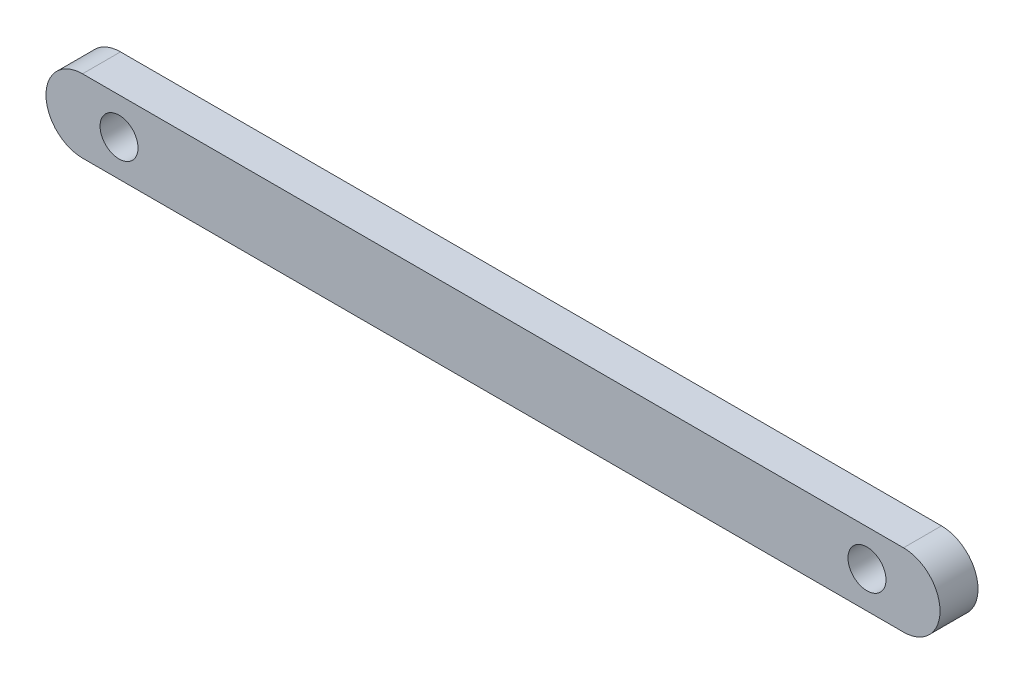
SolidWorks part; units mm, degrees
material "1060 Alloy"
ref_plane "Front Plane" through (0, 0, 0) normal (0, 0, 1) x (1, 0, 0)
ref_plane "Top Plane" through (0, 0, 0) normal (0, 1, 0) x (1, 0, 0)
ref_plane "Right Plane" through (0, 0, 0) normal (1, 0, 0) x (0, 0, -1)
ref_axis "X-axis" through (-88.99, 0, 0) along (1, 0, 0)
ref_axis "Y-axis" through (0, 55, 0) along (0, -1, 0)
ref_axis "Z-axis" through (0, 0, -88.99) along (0, 0, 1)
sketch "Sketch1" plane through (0, 0, 0) normal (0, 0, 1) x (1, 0, 0)
  line L0 (35.687, 0) -> (-35.687, 0) construction
  line L1 (35.687, -3.175) -> (-35.687, -3.175)
  line L2 (35.687, 3.175) -> (-35.687, 3.175)
  arc A0 (35.687, -3.175) -> (35.687, 3.175) centre (35.687, 0) ccw
  arc A1 (-35.687, 3.175) -> (-35.687, -3.175) centre (-35.687, 0) ccw
  point P2 (0, 0)
  point P8 (38.862, 0)
  point P9 (-38.862, 0)
  dimension "D1" = 6.35
  dimension "D2" = 77.724
extrude "Boss-Extrude1" add sketch "Sketch1" against normal blind 3.302
hole_wizard "1/4 (0.13) Diameter Hole1" positions "Sketch2" profile "Sketch3" hole size "1/4" standard "ANSI Inch" end condition through all
sketch "Sketch2" plane through (0, 0, 0) normal (0, 0, 1) x (1, 0, 0)
  line L0 (-32.512, 0) -> (32.512, 0) construction
  arc A0 (-35.687, 3.175) -> (-35.687, -3.175) centre (-35.687, 0) ccw construction
  point P0 (-32.512, 0)
  point P2 (32.512, 0)
  point P12 (-38.862, 0)
  dimension "D1" = 65.024
  dimension "D2" = 6.35
sketch "Sketch3" plane through (-32.512, 0, 0) normal (1, 0, 0) x (0, -1, 0)
  line L0 (0, 0) -> (0, 3.302)
  line L1 (0, 3.302) -> (1.651, 3.302)
  line L2 (1.651, 3.302) -> (1.651, 0)
  line L5 (1.651, 0) -> (0, 0)
  line L11 (0, -6.35) -> (0, 107.95) construction
  dimension "Thru Hole Dia." = 3.302
  dimension "Thru Hole Depth" = 3.302
